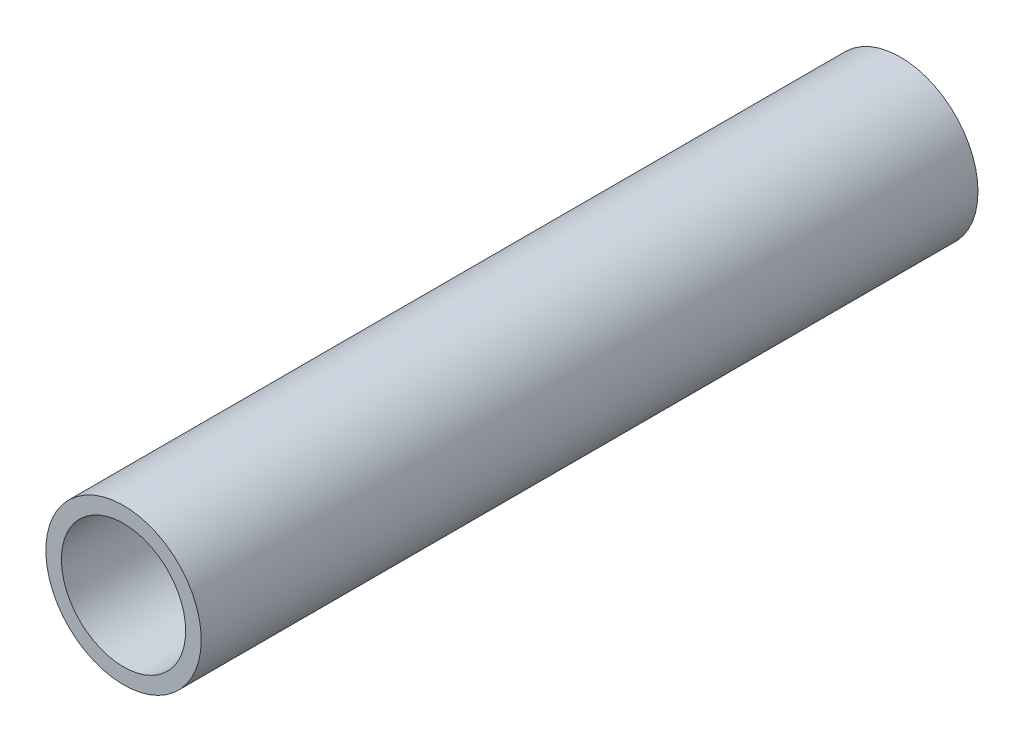
SolidWorks part; units mm, degrees
ref_plane "前视基准面" through (0, 0, 0) normal (0, 0, 1) x (1, 0, 0)
ref_plane "上视基准面" through (0, 0, 0) normal (0, 1, 0) x (1, 0, 0)
ref_plane "右视基准面" through (0, 0, 0) normal (1, 0, 0) x (0, 0, -1)
other "Configuration Table"
sketch "Sketch1" plane through (0, 0, 0) normal (0, 0, 1) x (1, 0, 0)
  circle A0 centre (0, 0) radius 20
  circle A1 centre (0, 0) radius 16
extrude "Boss-Extrude1" add sketch "Sketch1" along normal blind 200
sketch3d "3DSketch1"
  line L0 (0, 0, 0) -> (0, 0, 200) construction
ref_axis "outer_tube_center_axis" through (0, 0, 0) along (0, 0, 1)
ref_plane "outer_tube_bottom_face" through (0, 0, 0) normal (0, 0, 1) x (1, 0, 0)
ref_plane "outer_tube_top_face" through (0, 0, 200) normal (0, 0, 1) x (1, 0, 0)
